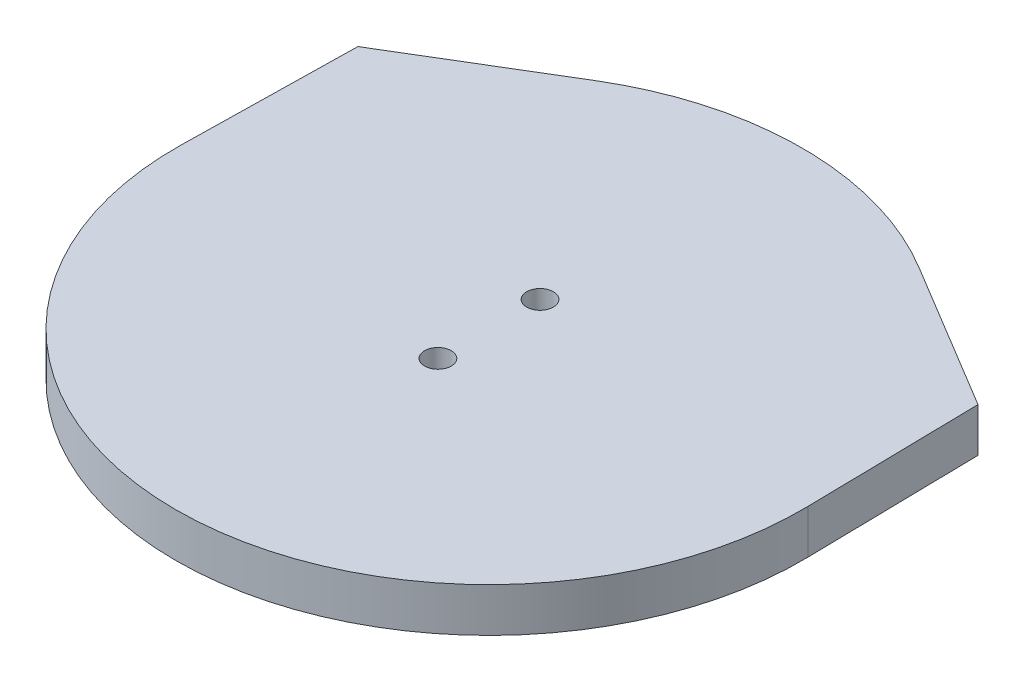
SolidWorks part; units mm, degrees
ref_plane "Front Plane" through (0, 0, 0) normal (0, 0, 1) x (1, 0, 0)
ref_plane "Top Plane" through (0, 0, 0) normal (0, 1, 0) x (1, 0, 0)
ref_plane "Right Plane" through (0, 0, 0) normal (1, 0, 0) x (0, 0, -1)
sketch "Sketch6" plane through (0, 0, 0) normal (0, 1, 0) x (1, 0, 0)
  line L8 (-37.735, 17.5894) -> (-18.833, 28.9671)
  line L9 (41.197, 17.5894) -> (22.295, 28.9671)
  line L10 (41.197, 17.5894) -> (41.5994, -4.4691)
  line L11 (-38.1374, -4.4691) -> (-37.735, 17.5894)
  arc A4 (22.295, 28.9671) -> (-18.833, 28.9671) centre (1.731, -5.1963) ccw
  circle A5 centre (1.731, 94.8037) radius 25 construction
  arc A6 (-38.1374, -4.4691) -> (41.5994, -4.4691) centre (1.731, -5.1963) ccw
  point P39 (-42.5504, 25.0018)
  point P40 (23.25, 50)
  point P41 (0, 50)
  point P42 (-20.8013, 25)
  point P43 (-20.0513, 25)
  point P45 (-43.3013, 25)
  point P46 (22.5, 50)
  point P51 (0, 50)
extrude "Boss-Extrude4" add sketch "Sketch6" along normal blind 5.6 separate body
sketch "Sketch8" plane through (0, 0, 0) normal (0, 1, 0) x (1, 0, 0)
  line L0 (1.731, 94.8037) -> (1.731, -25.8418) construction
  line L2 (1.731, -5.1963) -> (73.5507, -5.1963) construction
  circle A0 centre (1.731, 94.8037) radius 25 construction
  circle A1 centre (1.731, -5.1963) radius 12.7 construction
  circle A2 centre (1.731, -5.1963) radius 6.5 construction
  dimension "D1" = 13
hole_wizard "CSK for M3 Flat Head Machine Screw1" positions "Sketch14" profile "Sketch13" countersink size "M3" standard "ANSI Metric" end condition through all
sketch "Sketch14" plane through (0, 0, 5.6) normal (0, -1, 0) x (1, 0, 0)
  line L0 (1.731, -100.4037) -> (1.731, 20.2418) construction
  circle A0 centre (1.731, -0.4037) radius 6.5 construction
  point P0 (1.731, -6.9037)
  point P6 (1.731, 6.0963)
sketch "Sketch13" plane through (1.731, 0, -1.3037) normal (1, 0, 0) x (0, 0, -1)
  line L0 (0, 0) -> (0, 5.6)
  line L1 (0, 5.6) -> (1.7, 5.6)
  line L2 (1.7, 5.6) -> (1.7, 1.45)
  line L3 (1.7, 1.45) -> (3.15, 0)
  line L5 (3.15, 0) -> (0, 0)
  line L6 (-1.7, 1.45) -> (-3.15, 0) construction
  line L11 (0, -6.35) -> (0, 107.95) construction
  dimension "Thru Hole Dia." = 3.4
  dimension "Thru Hole Depth" = 5.6
  dimension "Near C'Sink Dia." = 6.3
  dimension "Near C'Sink Angle" = 90
